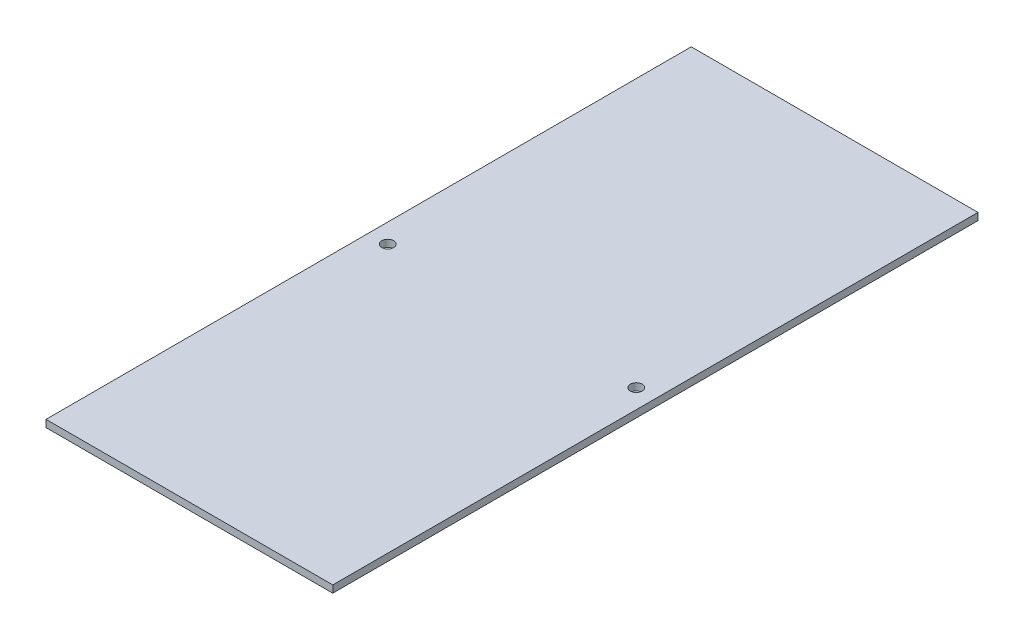
SolidWorks part; units mm, degrees
note: The reader was unsure of these and kept them because the rebuilt part matched: thickness of "Base-Flange1", "Sheet-Metal(1)", "Sheet-Metal(2)".
ref_plane "Front Plane" through (0, 0, 0) normal (0, 0, 1) x (1, 0, 0)
ref_plane "Top Plane" through (0, 0, 0) normal (0, 1, 0) x (1, 0, 0)
ref_plane "Right Plane" through (0, 0, 0) normal (1, 0, 0) x (0, 0, -1)
sketch "Sketch1" plane through (0, 0, 0) normal (0, 1, 0) x (1, 0, 0)
  line L1 (-60, -135) -> (60, -135)
  line L2 (-60, -135) -> (-60, 135)
  line L3 (-60, 135) -> (60, 135)
  line L4 (60, -135) -> (60, 135)
  line L5 (-60, -135) -> (60, 135) construction
  line L6 (-60, 135) -> (60, -135) construction
  point P0 (0, 0)
  dimension "D1" = 120
  dimension "D2" = 270
base flange "Base-Flange1" sketch "Sketch1" thickness 3 reverse thickness direction no parameters "D1"=0.5
sketch "Sketch6" plane through (0, 0, 0) normal (0, 1, 0) x (1, 0, 0)
  line L0 (-60, 135) -> (-60, -135) construction
  line L1 (60, -135) -> (60, 135) construction
  circle A0 centre (-52, 0) radius 2.5
  circle A1 centre (52, 0) radius 2.5
  dimension "D1" = 8
  dimension "D2" = 8
  dimension "D3" = 5
extrude "Cut-Extrude1" cut sketch "Sketch6" against normal blind 10 normal cut yes
sketch "Bend-Lines1" plane through (0, 0, 0) normal (0, 1, 0) x (1, 0, 0)
sketch "Bounding-Box1" plane through (0, 0, 0) normal (0, 1, 0) x (1, 0, 0)
sheet metal parameters "Sheet-Metal(1)" thickness 3 parameters "D1"=0.5
flat pattern "Flat-Pattern(1)" [suppressed]
sketch "Bend-Lines2" plane through (0, 0, 0) normal (0, 1, 0) x (1, 0, 0)
sketch "Bounding-Box2" [suppressed] plane through (0, 0, 0) normal (0, 1, 0) x (1, 0, 0)
sheet metal parameters "Sheet-Metal(2)" thickness 3 parameters "D1"=0.5
flat pattern "Flat-Pattern(1)"
sketch "Bend-Lines3" plane through (0, 0, 0) normal (0, 1, 0) x (1, 0, 0)
sketch "Bounding-Box3" [suppressed] plane through (0, 0, 0) normal (0, 1, 0) x (1, 0, 0)
